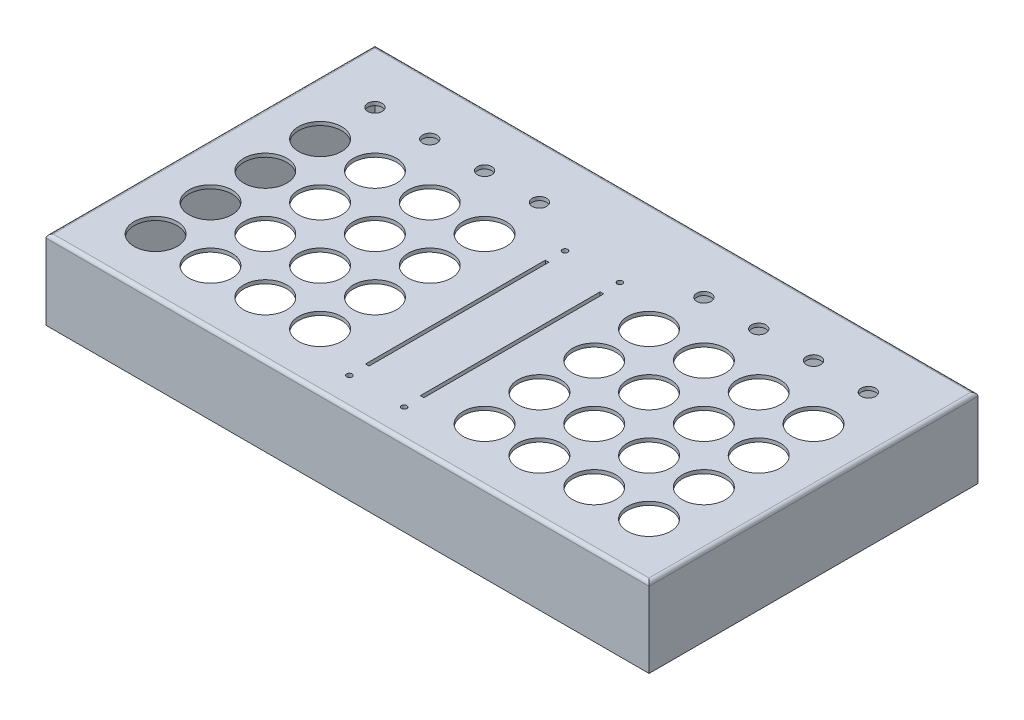
SolidWorks part; units mm, degrees
material "ABS"
ref_plane "Front Plane" through (0, 0, 0) normal (0, 0, 1) x (1, 0, 0)
ref_plane "Top Plane" through (0, 0, 0) normal (0, 1, 0) x (1, 0, 0)
ref_plane "Right Plane" through (0, 0, 0) normal (1, 0, 0) x (0, 0, -1)
sketch "Sketch2" plane through (0, 0, 0) normal (0, 1, 0) x (1, 0, 0)
  line L0 (0, 0) -> (91.5, 0) construction
  line L1 (0, 0) -> (0, 91.5) construction
  line L2 (122, 105.75) -> (122, -14.25) construction
  line L3 (121, 95.75) -> (123, 95.75)
  line L4 (121, 95.75) -> (121, -4.25)
  line L5 (121, -4.25) -> (123, -4.25)
  line L6 (123, 95.75) -> (123, -4.25)
  line L7 (91.5, 45.75) -> (137.25, 45.75) construction
  line L8 (91.5, 30.5) -> (91.5, 61) construction
  line L9 (0, 91.5) -> (0, 122) construction
  line L10 (0, 122) -> (91.5, 122) construction
  line L11 (0, 122) -> (30.5, 122) construction
  line L12 (137.25, -28.4189) -> (137.25, 162.5507) construction
  line L13 (274.5, 122) -> (244, 122) construction
  line L14 (274.5, 122) -> (183, 122) construction
  line L15 (274.5, 91.5) -> (274.5, 122) construction
  line L16 (183, 30.5) -> (183, 61) construction
  line L17 (152.5, 105.75) -> (152.5, -14.25) construction
  line L18 (274.5, 0) -> (274.5, 91.5) construction
  line L19 (274.5, 0) -> (183, 0) construction
  line L20 (151.5, 95.75) -> (151.5, -4.25)
  line L21 (153.5, -4.25) -> (151.5, -4.25)
  line L22 (153.5, 95.75) -> (153.5, -4.25)
  line L23 (153.5, 95.75) -> (151.5, 95.75)
  line L25 (-30.5, -30.5) -> (305, -30.5)
  line L26 (-30.5, -30.5) -> (-30.5, 152.5)
  line L27 (-30.5, 152.5) -> (305, 152.5)
  line L28 (305, -30.5) -> (305, 152.5)
  circle A0 centre (0, 0) radius 12
  circle A1 centre (30.5, 0) radius 12
  circle A2 centre (61, 0) radius 12
  circle A3 centre (91.5, 0) radius 12
  circle A4 centre (30.5, 30.5) radius 12
  circle A5 centre (61, 30.5) radius 12
  circle A6 centre (91.5, 30.5) radius 12
  circle A7 centre (30.5, 61) radius 12
  circle A8 centre (61, 61) radius 12
  circle A9 centre (91.5, 61) radius 12
  circle A10 centre (30.5, 91.5) radius 12
  circle A11 centre (61, 91.5) radius 12
  circle A12 centre (91.5, 91.5) radius 12
  circle A13 centre (0, 30.5) radius 12
  circle A14 centre (0, 61) radius 12
  circle A15 centre (0, 91.5) radius 12
  circle A16 centre (122, 105.75) radius 1.5
  circle A17 centre (122, -14.25) radius 1.5
  circle A18 centre (0, 122) radius 4
  circle A19 centre (30.5, 122) radius 4
  circle A20 centre (61, 122) radius 4
  circle A21 centre (91.5, 122) radius 4
  circle A22 centre (183, 122) radius 4
  circle A23 centre (213.5, 122) radius 4
  circle A24 centre (244, 122) radius 4
  circle A25 centre (274.5, 122) radius 4
  circle A26 centre (152.5, -14.25) radius 1.5
  circle A27 centre (152.5, 105.75) radius 1.5
  circle A28 centre (274.5, 91.5) radius 12
  circle A29 centre (274.5, 61) radius 12
  circle A30 centre (274.5, 30.5) radius 12
  circle A31 centre (183, 91.5) radius 12
  circle A32 centre (213.5, 91.5) radius 12
  circle A33 centre (244, 91.5) radius 12
  circle A34 centre (183, 61) radius 12
  circle A35 centre (213.5, 61) radius 12
  circle A36 centre (244, 61) radius 12
  circle A37 centre (183, 30.5) radius 12
  circle A38 centre (213.5, 30.5) radius 12
  circle A39 centre (244, 30.5) radius 12
  circle A40 centre (183, 0) radius 12
  circle A41 centre (213.5, 0) radius 12
  circle A42 centre (244, 0) radius 12
  circle A43 centre (274.5, 0) radius 12
  point P41 (122, 95.75)
  point P42 (121, 45.75)
  point P105 (153.5, 45.75)
  point P106 (152.5, 95.75)
  dimension "D1" = 24
  dimension "D8" = 3
  dimension "D12" = 8
  dimension "D4" = 30.5
  dimension "D5" = 30.5
  dimension "D6" = 100
  dimension "D7" = 2
  dimension "D9" = 10
  dimension "D10" = 10
  dimension "D11" = 30.5
  dimension "D14" = 30.5
  dimension "D15" = 30.5
  dimension "D16" = 15.25
  dimension "D17" = 30.5
  dimension "D18" = 30.5
  dimension "D19" = 30.5
  dimension "D20" = 30.5
  dimension "D2" = 4
  dimension "D3" = 4
  dimension "D13" = 4
extrude "Boss-Extrude1" add sketch "Sketch2" along normal blind 44
shell "Shell1" thickness 2 removed face at (244, 0, -12) removed face at (0, 44, 12) removed face at (30.5, 44, 12) removed face at (61, 44, 12) removed face at (91.5, 44, 12) removed face at (91.5, 44, -18.5) removed face at (61, 44, -18.5) removed face at (30.5, 44, -18.5) removed face at (0, 44, -18.5) removed face at (0, 44, -49) removed face at (0, 44, -79.5) removed face at (30.5, 44, -79.5) removed face at (30.5, 44, -49) removed face at (61, 44, -49) removed face at (61, 44, -79.5) removed face at (91.5, 44, -79.5) removed face at (91.5, 44, -49) removed face at (0, 44, -118) removed face at (30.5, 44, -118) removed face at (91.5, 44, -118) removed face at (61, 44, -118) removed face at (122, 44, -104.25) removed face at (152.5, 44, -107.25) removed face at (183, 44, -126) removed face at (183, 44, -103.5) removed face at (213.5, 44, -103.5) removed face at (213.5, 44, -126) removed face at (183, 44, -73) removed face at (183, 44, -42.5) removed face at (183, 44, -12) removed face at (213.5, 44, -12) removed face at (213.5, 44, -42.5) removed face at (213.5, 44, -73) removed face at (244, 44, -73) removed face at (244, 44, -42.5) removed face at (244, 44, -12) removed face at (274.5, 44, -12) removed face at (274.5, 44, -42.5) removed face at (274.5, 44, -73) removed face at (274.5, 44, -103.5) removed face at (244, 44, -103.5) removed face at (244, 44, -126) removed face at (274.5, 44, -126) removed face at (152.5, 44, 12.75) removed face at (122, 44, 15.75) removed face at (153.5, 22, -45.75) removed face at (152.5, 22, -95.75) removed face at (122, 22, -95.75) removed face at (123, 22, -45.75) removed face at (121, 22, -45.75) removed face at (122, 22, 4.25) removed face at (151.5, 22, -45.75) removed face at (152.5, 22, 4.25)
fillet "Fillet1" radius 2 4 edges at (-30.5, 44, -61) (137.25, 44, 30.5) (305, 44, -61) (137.25, 44, -152.5)
sketch "Sketch3" plane through (0, 42, 0) normal (0, -1, 0) x (1, 0, 0)
  line L0 (12, -122) -> (42.5, -122) construction
  line L1 (195, -122) -> (225.5, -122) construction
  circle A0 centre (0, -122) radius 4 construction
  circle A1 centre (12, -122) radius 0.5
  circle A2 centre (42.5, -122) radius 0.5
  circle A3 centre (73, -122) radius 0.5
  circle A4 centre (103.5, -122) radius 0.5
  circle A5 centre (183, -122) radius 4 construction
  circle A6 centre (195, -122) radius 0.5
  circle A7 centre (225.5, -122) radius 0.5
  circle A8 centre (256, -122) radius 0.5
  circle A9 centre (286.5, -122) radius 0.5
  dimension "D2" = 1
  dimension "D6" = 1
  dimension "D1" = 12
  dimension "D4" = 30.5
  dimension "D5" = 12
  dimension "D8" = 30.5
  dimension "D3" = 4
  dimension "D7" = 4
extrude "Cut-Extrude1" cut sketch "Sketch3" against normal blind 1
